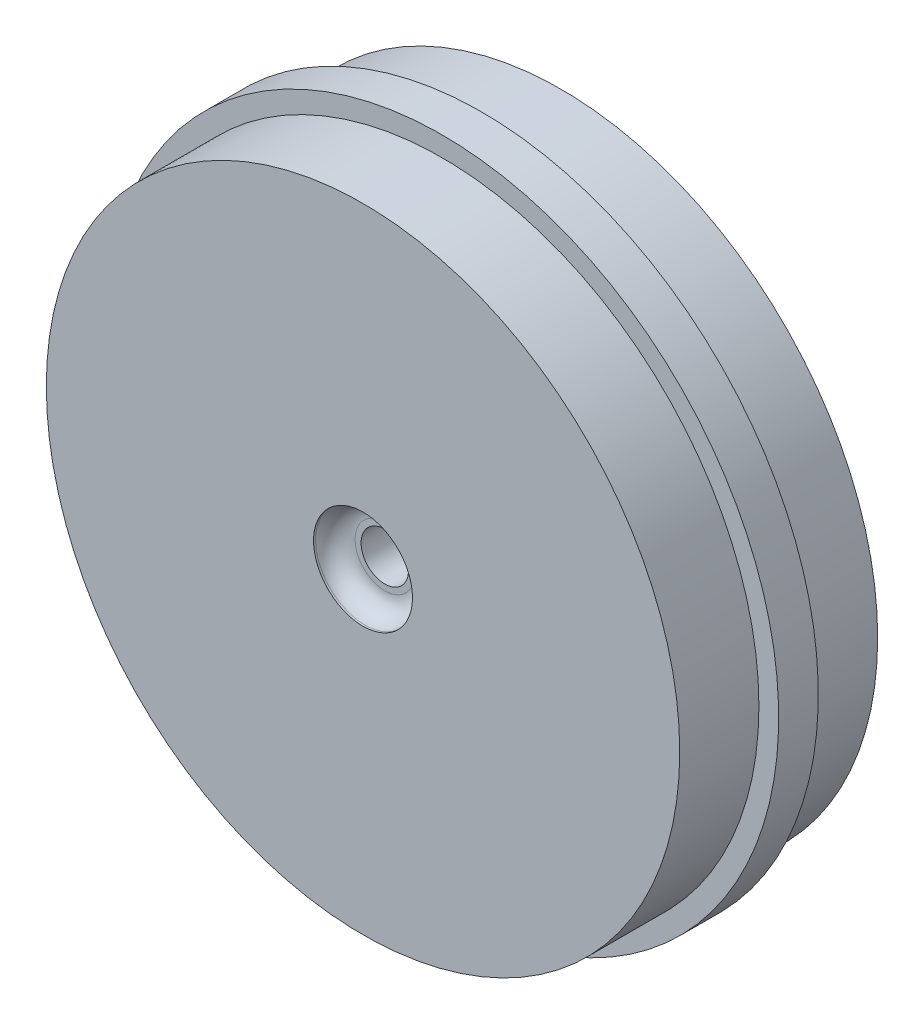
SolidWorks part; units mm, degrees
material "PET"
ref_plane "Plan de face" through (0, 0, 0) normal (0, 0, 1) x (1, 0, 0)
ref_plane "Plan de dessus" through (0, 0, 0) normal (0, 1, 0) x (1, 0, 0)
ref_plane "Plan de droite" through (0, 0, 0) normal (1, 0, 0) x (0, 0, -1)
sketch "Esquisse1" plane through (0, 0, 0) normal (0, 0, 1) x (1, 0, 0)
  circle A0 centre (0, 0) radius 14.5
  dimension "D1" = 29
extrude "Boss.-Extru.1" add sketch "Esquisse1" along normal blind 10
sketch "Esquisse2" plane through (0, 0, 0) normal (0, 0, 1) x (1, 0, 0)
  circle A0 centre (0, 0) radius 16.5
  dimension "D1" = 33
extrude "Boss.-Extru.2" add sketch "Esquisse2" along normal offset from surface (8 mm away) 1 from offset 1 up to face at (14.5, 0, 10)
sketch "Esquisse6" plane through (0, 0, 10) normal (0, 0, 1) x (1, 0, 0)
  circle A0 centre (0, 0) radius 13.5
  dimension "D1" = 27
extrude "Enlèv. mat.-Extru.4" cut sketch "Esquisse6" against normal blind 1
hole_wizard "Chambrage pour vis à tête ronde bombée M21" positions "Esquisse9" profile "Esquisse8" counterbore size "M2" standard "Ansi Metric" end condition through all
sketch "Esquisse9" plane through (0, 0, 9) normal (0, 0, 1) x (1, 0, 0)
  point P0 (0, 0)
sketch "Esquisse8" plane through (0, 0, 9) normal (1, 0, 0) x (0, -1, 0)
  line L0 (0, 0) -> (0, 9)
  line L1 (0, 9) -> (1.2, 9)
  line L3 (1.2, 9) -> (1.2, 1.6)
  line L4 (1.2, 1.6) -> (2.5, 1.6)
  line L5 (2.5, 1.6) -> (2.5, 0)
  line L7 (2.5, 0) -> (0, 0)
  line L11 (0, -6.35) -> (0, 107.95) construction
  dimension "Diamètre du perçage jusqu'au prochain" = 2.4
  dimension "Profondeur du perçage jusqu'au prochain" = 9
  dimension "Diamètre du chambrage" = 5
  dimension "Profondeur du chambrage" = 1.6
sketch "Esquisse13" plane through (0, 0, 0) normal (0, 0, -1) x (-1, 0, 0)
  circle A0 centre (0, 0) radius 13.5
  circle A1 centre (0, 0) radius 4.2
  dimension "D1" = 27
  dimension "D2" = 8.4
extrude "Enlèv. mat.-Extru.7" cut sketch "Esquisse13" against normal offset from surface (7 mm away) 2 up to face at (2.5, 0, 9)
sketch "Esquisse15" plane through (0, 0, 0) normal (0, 0, -1) x (-1, 0, 0)
  line L0 (-1.95, 2.0785) -> (-1.95, -2.0785)
  line L1 (1.95, 2.0785) -> (1.95, -2.0785)
  arc A0 (-1.95, -2.0785) -> (1.95, -2.0785) centre (0, 0) ccw
  arc A1 (1.95, 2.0785) -> (-1.95, 2.0785) centre (0, 0) ccw
  dimension "D1" = 5.7
  dimension "D2" = 1.95
  dimension "D3" = 1.95
extrude "Enlèv. mat.-Extru.8" cut sketch "Esquisse15" against normal blind 7
sketch "Sketch2" plane through (0, 0, 1) normal (0, 0, -1) x (-1, 0, 0)
  circle A0 centre (0, 0) radius 16.5
  circle A1 centre (0, 0) radius 14.5
extrude "Boss-Extrude2" add sketch "Sketch2" along normal up to surface (1 mm away) and the other way up to surface (9 mm away) up to face at (0, 0, 0) other way up to face at (13.5, 0, 10)
sketch "Sketch3" plane through (0, 0, 0) normal (0, 0, -1) x (-1, 0, 0)
  circle A0 centre (0, 0) radius 16.5
  circle A1 centre (0, 0) radius 22.5
  dimension "D1" = 6
extrude "Boss-Extrude3" add sketch "Sketch3" against normal up to surface (10 mm away) up to face at (13.5, 0, 10)
fillet "Fillet1" radius 1 2 edges at (-22.5, 0, 0) (22.5, 0, 10)
ref_plane "Plane1" through (0, 0, 0) normal (1, 0, 0) x (0, 0, -1)
sketch "Sketch4" plane through (0, 0, 0) normal (1, 0, 0) x (0, 0, -1)
  line L0 (-9, 22.5) -> (-1, 22.5) construction
  line L1 (-1, 22.5) -> (-9, 22.5) construction
  line L2 (-9, 22.5) -> (-9, 18)
  line L3 (-5, 22.5) -> (-5, 24.473) construction
  line L4 (-9, 18) -> (-1, 18)
  line L5 (-1, 18) -> (-1, 22.5)
  arc A0 (-9, 22.5) -> (-1, 22.5) centre (-5, 14.0611) cw
  point P10 (-5, 23.4)
  dimension "D2" = 0.9
extrude "Boss-Extrude4" add sketch "Sketch4" along normal blind 0.5 and the other way blind 0.5
pattern_circular "CirPattern1" count 70 over 360 about axis through (0, 0, 73.6396) along (0, 0, -1) of "Boss-Extrude4"
sketch "Sketch5" plane through (0, 0, 0) normal (0, 0, -1) x (-1, 0, 0)
  circle A0 centre (0, 0) radius 16
  circle A1 centre (0, 0) radius 40
  dimension "D1" = 32
  dimension "D2" = 80
extrude "Cut-Extrude1" cut sketch "Sketch5" against normal blind 20
sketch "Sketch6" plane through (0, 0, 0) normal (0, 0, -1) x (-1, 0, 0)
  circle A0 centre (0, 0) radius 16
  circle A1 centre (0, 0) radius 17
  circle A2 centre (0, 0) radius 16 construction
  dimension "D1" = 1
extrude "Boss-Extrude5" add sketch "Sketch6" against normal blind 2 from offset 4 offset against normal yes
sketch "Sketch8" plane through (0, 0, 9) normal (0, 0, 1) x (1, 0, 0)
  circle A0 centre (0, 0) radius 13.5
  circle A1 centre (0, 0) radius 2.5
  circle A2 centre (0, 0) radius 13.5 construction
  circle A3 centre (0, 0) radius 2.5 construction
extrude "Boss-Extrude6" add sketch "Sketch8" along normal up to surface (1 mm away) up to face at (13.5, 0, 10)
sketch "Sketch9" plane through (0, 0, 7.4) normal (0, 0, 1) x (1, 0, 0)
  circle A0 centre (0, 0) radius 2.5
  circle A1 centre (0, 0) radius 1.2
  circle A2 centre (0, 0) radius 1.2 construction
  circle A3 centre (0, 0) radius 2.5 construction
extrude "Boss-Extrude7" add sketch "Sketch9" along normal blind 1.5
fillet "Fillet2" radius 1 1 edges at (2.5, 0, 8.9)
